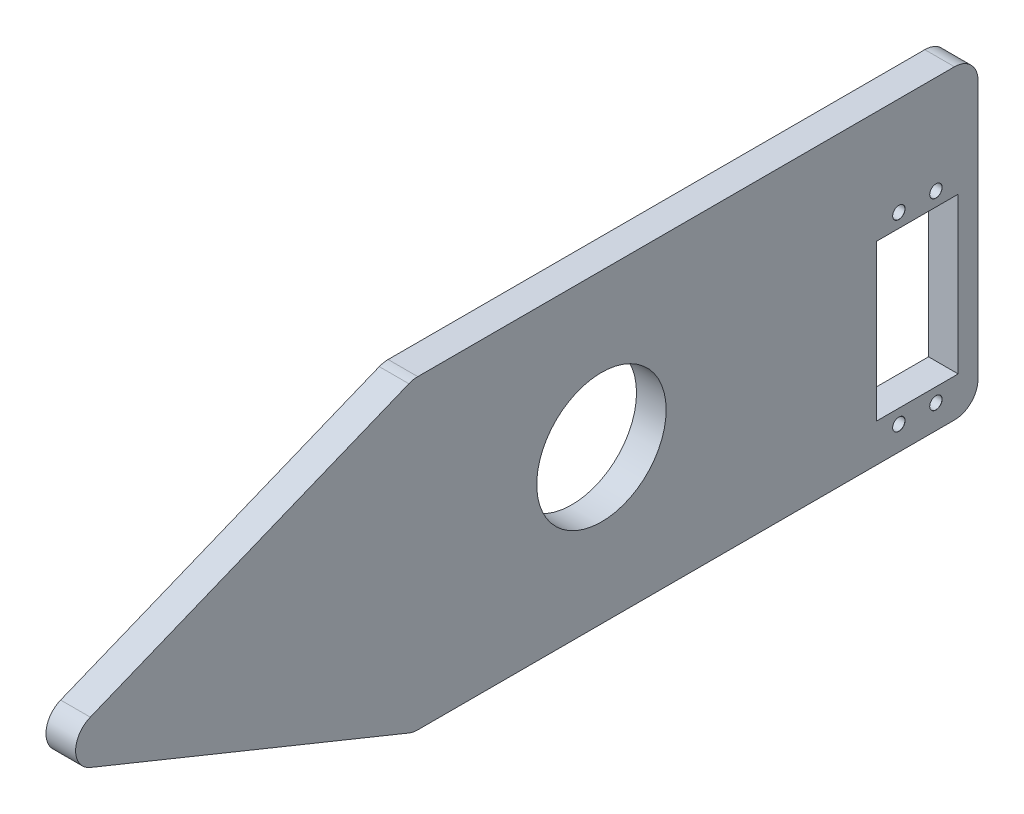
SolidWorks part; units mm, degrees
ref_plane "Front Plane" through (0, 0, 0) normal (1, 0, 0) x (0, 1, 0)
ref_plane "Top Plane" through (0, 0, 0) normal (0, 0, 1) x (0, 1, 0)
ref_plane "Right Plane" through (0, 0, 0) normal (0, 1, 0) x (-1, 0, 0)
sketch "Sketch1" plane through (0, 0, 0) normal (1, 0, 0) x (0, 1, 0)
  line L0 (-41.275, 50.8) -> (-41.275, -101.6)
  line L1 (-41.275, -101.6) -> (41.275, -101.6)
  line L2 (41.275, -101.6) -> (41.275, 50.8)
  line L3 (41.275, 50.8) -> (0, 152.4)
  line L4 (0, 152.4) -> (-41.275, 50.8)
  line L5 (0, 152.4) -> (0, 0) construction
  line L6 (-41.275, 50.8) -> (0, 50.8) construction
  line L7 (0, 50.8) -> (41.275, 50.8) construction
  circle A0 centre (0, 0) radius 6.35 construction
  circle A1 centre (0, 0) radius 17.4625
  dimension "D5" = 12.7
  dimension "D6" = 34.925
  dimension "D1" = 152.4
  dimension "D2" = 254
  dimension "D3" = 101.6
  dimension "D4" = 82.55
sketch "Sketch2" plane through (0, 0, 0) normal (1, 0, 0) x (0, 1, 0)
  line L0 (-37.25, -85.25) -> (-30, -85.25) construction
  line L1 (-30, -75.25) -> (10, -75.25)
  line L2 (-30, -75.25) -> (-30, -95.25)
  line L3 (-30, -95.25) -> (10, -95.25)
  line L9 (-30, -76.25) -> (-37.25, -76.25)
  line L10 (-30, -76.25) -> (-30, -94.25)
  line L11 (-30, -94.25) -> (-37.25, -94.25)
  line L12 (-37.25, -76.25) -> (-37.25, -94.25)
  line L13 (10, -75.25) -> (10, -95.25)
  line L14 (-10, -75.25) -> (-10, -95.25) construction
  line L15 (10, -94.25) -> (17.25, -94.25)
  line L16 (17.25, -76.25) -> (17.25, -94.25)
  line L17 (10, -76.25) -> (17.25, -76.25)
  line L18 (-34.75, -76.25) -> (-34.75, -80.25) construction
  line L19 (-34.75, -80.25) -> (-34.75, -90.25) construction
  line L20 (-34.75, -90.25) -> (-34.75, -94.25) construction
  line L21 (14.75, -90.25) -> (14.75, -94.25) construction
  line L22 (14.75, -80.25) -> (14.75, -90.25) construction
  line L23 (14.75, -76.25) -> (14.75, -80.25) construction
  line L24 (0, -85.25) -> (10, -85.25) construction
  line L25 (0, 0) -> (0, -85.25) construction
  line L26 (-41.275, -101.6) -> (41.275, -101.6) construction
  circle A0 centre (0, -85.25) radius 3.9853
  circle A1 centre (-34.75, -80.25) radius 2.1
  dimension "D9" = 4.2
  dimension "D1" = 40
  dimension "D2" = 54.5
  dimension "D3" = 10
  dimension "D4" = 49.5
  dimension "D5" = 20
  dimension "D6" = 1
  dimension "D7" = 10
  dimension "D8" = 6.35
extrude "Boss-Extrude2" add sketch "Sketch1" along normal mid plane 8.001
fillet "Fillet1" radius 6.35 5 edges at (0, 41.275, -101.6) (0, -41.275, -101.6) (0, 0, 152.4) (0, -41.275, 50.8) (0, 41.275, 50.8)
hole_wizard "Tap Drill for M4x0.7 Tap1" positions "Sketch3" profile "Sketch4" hole size "M4x0.7" standard "ANSI Metric" end condition through all
sketch "Sketch3" plane through (4.0005, 0, 0) normal (1, 0, 0) x (0, 1, 0)
  point P0 (-34.75, -80.25)
  point P3 (-34.75, -90.25)
  point P6 (14.75, -80.25)
  point P9 (14.75, -90.25)
sketch "Sketch4" plane through (4.0005, -34.75, -80.25) normal (0, 1, 0) x (0, 0, -1)
  line L0 (0, 0) -> (0, 8.001)
  line L1 (0, 8.001) -> (1.65, 8.001)
  line L2 (1.65, 8.001) -> (1.65, 0.025)
  line L3 (1.65, 0.025) -> (1.675, 0)
  line L5 (1.675, 0) -> (0, 0)
  line L6 (-1.65, 0.025) -> (-1.675, 0) construction
  line L11 (0, -6.35) -> (0, 107.95) construction
  dimension "Thru Hole Dia." = 3.3
  dimension "Thru Hole Depth" = 8.001
  dimension "Near C'Sink Dia." = 3.35
  dimension "Near C'Sink Angle" = 90
sketch "Sketch5" plane through (4.0005, 0, 0) normal (1, 0, 0) x (0, 1, 0)
  line L8 (11, -96.25) -> (11, -74.25)
  line L9 (-31, -96.25) -> (11, -96.25)
  line L10 (-31, -74.25) -> (-31, -96.25)
  line L11 (11, -74.25) -> (-31, -74.25)
  line L12 (11, -96.25) -> (11, -74.25)
  line L13 (-31, -96.25) -> (11, -96.25)
  line L14 (-31, -74.25) -> (-31, -96.25)
  line L15 (11, -74.25) -> (-31, -74.25)
  dimension "D1" = 1
extrude "Cut-Extrude1" cut sketch "Sketch5" against normal through all
